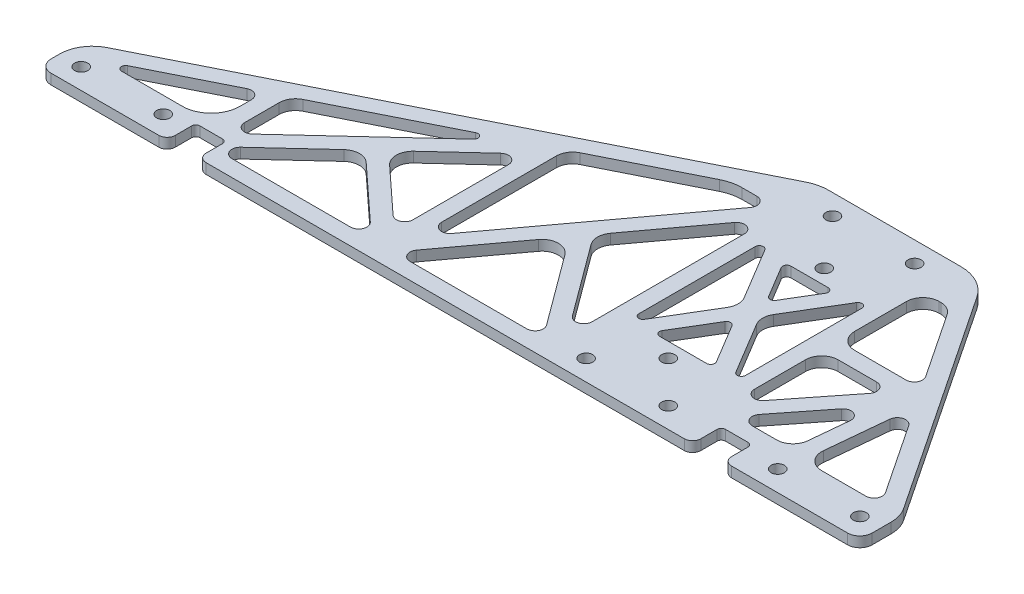
SolidWorks part; units mm, degrees
ref_plane "Front Plane" through (0, 0, 0) normal (0, 0, 1) x (1, 0, 0)
ref_plane "Top Plane" through (0, 0, 0) normal (0, 1, 0) x (1, 0, 0)
ref_plane "Right Plane" through (0, 0, 0) normal (1, 0, 0) x (0, 0, -1)
sketch "Sketch1" plane through (0, 0, 0) normal (0, 1, 0) x (1, 0, 0)
  line L0 (0, 0) -> (254, 0)
  line L2 (203.2, 88.9) -> (152.4, 88.9)
  line L4 (0, 0) -> (0, 12.7)
  line L5 (0, 12.7) -> (152.4, 88.9)
  line L6 (203.2, 88.9) -> (254, 12.7)
  line L7 (254, 12.7) -> (254, 0)
  line L8 (0, 6.35) -> (44.45, 6.35) construction
  line L9 (254, 6.35) -> (222.25, 6.35) construction
  line L10 (139.7, 82.55) -> (207.4333, 82.55) construction
  line L11 (44.45, 0) -> (44.45, 34.925) construction
  line L12 (156.6333, 12.7) -> (154.0933, 7.62)
  line L13 (224.7006, 47.4909) -> (221.314, 12.7) construction
  line L20 (127, 76.2) -> (211.6667, 76.2)
  line L21 (154.0933, 76.2) -> (101.6, 5.08) construction
  line L22 (154.0933, 12.7) -> (154.0933, 7.62)
  line L23 (247.8946, 12.7) -> (194.7333, 12.7)
  line L24 (224.7006, 47.4909) -> (197.2733, 12.7) construction
  line L28 (224.7006, 47.4909) -> (194.7333, 47.4909) construction
  line L31 (5.08, 9.5604) -> (153.5992, 83.82)
  line L32 (200.4813, 83.82) -> (153.5992, 83.82)
  line L33 (200.4813, 83.82) -> (248.92, 11.1619)
  line L34 (248.92, 11.1619) -> (248.92, 5.08)
  line L35 (5.08, 5.08) -> (248.92, 5.08)
  line L36 (5.08, 5.08) -> (5.08, 9.5604)
  line L37 (101.6, 5.08) -> (101.6, 57.8204) construction
  line L39 (127.8467, 40.64) -> (154.0933, 5.08) construction
  line L40 (101.6, 57.8204) -> (44.45, 5.08) construction
  line L41 (73.025, 31.4502) -> (101.6, 5.08) construction
  line L42 (154.0933, 7.62) -> (154.0933, 5.08)
  line L83 (152.8233, 5.08) -> (150.2833, 0)
  line L84 (125.803, 39.1316) -> (152.0497, 3.5716)
  line L107 (152.0497, 77.7084) -> (99.5564, 6.5884)
  line L108 (156.6333, 76.2) -> (194.7333, 12.7) construction
  line L113 (194.7333, 76.2) -> (156.6333, 12.7) construction
  line L117 (104.14, 5.08) -> (104.14, 63.6207)
  line L118 (156.6333, 12.7) -> (194.7333, 12.7)
  line L119 (194.7333, 12.7) -> (201.0833, 0)
  line L120 (154.0933, 6.35) -> (197.9083, 6.35) construction
  line L126 (192.5553, 77.5068) -> (154.4553, 14.0068)
  line L127 (154.4553, 74.8932) -> (192.5553, 11.3932)
  line L128 (156.6333, 12.7) -> (156.6333, 76.2) construction
  line L129 (194.7333, 12.7) -> (194.7333, 76.2) construction
  line L130 (197.2733, 12.7) -> (197.2733, 76.2)
  line L131 (159.1733, 12.7) -> (159.1733, 76.2)
  line L132 (192.1933, 12.7) -> (192.1933, 76.2)
  line L133 (154.0933, 12.7) -> (154.0933, 76.2)
  line L147 (196.9114, 74.8932) -> (158.8114, 11.3932)
  line L148 (158.8114, 77.5068) -> (196.9114, 14.0068)
  line L154 (104.14, 63.6207) -> (42.7274, 6.9466)
  line L155 (71.3024, 29.5836) -> (99.8774, 3.2134)
  line L156 (224.7006, 50.0309) -> (194.7333, 50.0309)
  line L157 (222.7059, 49.0635) -> (195.2786, 14.2725)
  line L158 (197.2733, 12.7) -> (197.2733, 7.62)
  line L159 (222.1726, 47.737) -> (218.7859, 12.9461)
  line L160 (129.8903, 42.1484) -> (156.137, 6.5884)
  line L163 (156.137, 74.6916) -> (103.6436, 3.5716)
  line L164 (99.06, 5.08) -> (99.06, 52.0201)
  line L165 (99.06, 52.0201) -> (46.1726, 3.2134)
  line L166 (175.6833, 19.05) -> (162.9833, 6.35) construction
  line L167 (175.6833, 19.05) -> (188.3833, 6.35) construction
  line L168 (162.9833, 82.55) -> (175.6833, 67.31) construction
  line L169 (175.6833, 67.31) -> (188.3833, 82.55) construction
  line L170 (161.6625, 21.082) -> (189.7041, 21.082) construction
  line L171 (161.6625, 23.622) -> (189.7041, 23.622)
  line L172 (163.1865, 65.278) -> (188.1801, 65.278) construction
  line L173 (163.1865, 62.738) -> (188.1801, 62.738)
  line L174 (74.7476, 33.3168) -> (103.3226, 6.9466)
  line L175 (224.7006, 44.9509) -> (194.7333, 44.9509)
  line L176 (226.6953, 45.9184) -> (199.268, 11.1275)
  line L177 (227.2287, 47.2449) -> (223.842, 12.4539)
  line L178 (8.8192, 11.43) -> (44.45, 11.43)
  line L179 (46.99, 0) -> (46.99, 34.925)
  line L180 (41.91, 0) -> (41.91, 34.925)
  line L181 (198.2745, 13.97) -> (221.4376, 13.97)
  circle A0 centre (6.7733, 6.35) radius 2.032
  circle A1 centre (32.1733, 6.35) radius 2.032
  circle A2 centre (222.25, 6.35) radius 2.032
  circle A3 centre (247.65, 6.35) radius 2.032
  circle A4 centre (162.9833, 82.55) radius 2.032
  circle A5 centre (188.3833, 82.55) radius 2.032
  circle A28 centre (162.9833, 6.35) radius 2.032
  circle A29 centre (188.3833, 6.35) radius 2.032
  arc A32 (197.2733, 12.7) -> (192.1933, 12.7) centre (194.7333, 12.7) cw
  arc A33 (197.2733, 76.2) -> (192.1933, 76.2) centre (194.7333, 76.2) ccw
  arc A34 (159.1733, 12.7) -> (154.0933, 12.7) centre (156.6333, 12.7) cw
  arc A35 (159.1733, 76.2) -> (154.0933, 76.2) centre (156.6333, 76.2) ccw
  arc A45 (192.5553, 77.5068) -> (196.9114, 74.8932) centre (194.7333, 76.2) cw
  arc A46 (154.4553, 14.0068) -> (158.8114, 11.3932) centre (156.6333, 12.7) ccw
  arc A47 (154.4553, 74.8932) -> (158.8114, 77.5068) centre (156.6333, 76.2) cw
  arc A48 (192.5553, 11.3932) -> (196.9114, 14.0068) centre (194.7333, 12.7) ccw
  circle A59 centre (175.6833, 19.05) radius 2.032
  circle A60 centre (175.6833, 67.31) radius 2.032
  arc A61 (125.803, 39.1316) -> (129.8903, 42.1484) centre (127.8467, 40.64) cw
  arc A62 (152.0497, 3.5716) -> (156.137, 6.5884) centre (154.0933, 5.08) ccw
  arc A63 (152.0497, 77.7084) -> (156.137, 74.6916) centre (154.0933, 76.2) cw
  arc A64 (99.5564, 6.5884) -> (103.6436, 3.5716) centre (101.6, 5.08) ccw
  arc A65 (104.14, 5.08) -> (99.06, 5.08) centre (101.6, 5.08) cw
  arc A66 (42.7274, 6.9466) -> (46.1726, 3.2134) centre (44.45, 5.08) ccw
  arc A67 (71.3024, 29.5836) -> (74.7476, 33.3168) centre (73.025, 31.4502) cw
  arc A68 (99.8774, 3.2134) -> (103.3226, 6.9466) centre (101.6, 5.08) ccw
  arc A69 (224.7006, 50.0309) -> (224.7006, 44.9509) centre (224.7006, 47.4909) cw
  arc A70 (194.7333, 50.0309) -> (194.7333, 44.9509) centre (194.7333, 47.4909) ccw
  arc A71 (222.7059, 49.0635) -> (226.6953, 45.9184) centre (224.7006, 47.4909) cw
  arc A72 (195.2786, 14.2725) -> (199.268, 11.1275) centre (197.2733, 12.7) ccw
  arc A73 (222.1726, 47.737) -> (227.2287, 47.2449) centre (224.7006, 47.4909) cw
  arc A74 (218.7859, 12.9461) -> (223.842, 12.4539) centre (221.314, 12.7) ccw
  arc A75 (46.99, 0) -> (41.91, 0) centre (44.45, 0) cw
  arc A76 (46.99, 34.925) -> (41.91, 34.925) centre (44.45, 34.925) ccw
  dimension "D7" = 4.064
  dimension "D8" = 25.4
  dimension "D9" = 130.81
  dimension "D10" = 25.4
  dimension "D11" = 6.35
  dimension "D13" = 19.05
  dimension "D1" = 254
  dimension "D2" = 50.8
  dimension "D3" = 88.9
  dimension "D4" = 152.4
  dimension "D5" = 12.7
  dimension "D6" = 6.35
  dimension "D12" = 25.4
  dimension "D14" = 44.45
  dimension "D15" = 12.7
  dimension "D16" = 57.15
  dimension "D18" = 12.7
  dimension "D19" = 2.54
  dimension "D20" = 50.8
  dimension "D21" = 25.4
  dimension "D22" = 2.54
  dimension "D23" = 6.35
  dimension "D24" = 2.54
  dimension "D29" = 6.35
  dimension "D30" = 38.1
  dimension "D31" = 25.4
  dimension "D32" = 6.35
  dimension "D33" = 2.54
  dimension "D36" = 12.7
  dimension "D38" = 15.24
  dimension "D39" = 2.54
  dimension "D40" = 2.54
  dimension "D27" = 1.27
  dimension "D17" = 5.08
  dimension "D25" = 2.54
  dimension "D26" = 2.54
  dimension "D37" = 2.54
extrude "Boss-Extrude1" add sketch "Sketch1" along normal blind 3.175 contours L0 L7 L6 L2 L5 L4 | A0 | A1 | A5 | A4 | A2 | A3
extrude "Cut-Extrude2" cut sketch "Sketch1<3>" along normal through all contours L154 L31 L11 | L155 L165 L35 | L165 L174 L164 | L117 L107 L20 L31 | L84 L163 L35 | L133 L163 L160 L22 | L157 L175 L130 | L156 L33 L20 L130 | L147 L148 L132 | L131 L126 L127 | L173 L148 L126 | L147 L171 L127 | L33 L177 L23 | L178 L180 L31 | L176 L181 L159 | A28 | A59 | A29 | A60 region at (30.8797, 0, -16.9451) region at (73.025, 0, -12.718) region at (62.4687, 0, -31.7097) region at (120.7695, 0, -51.2726) region at (127.8467, 0, -15.5076) region at (91.6301, 0, -31.4502) region at (206.5243, 0, -60.8789) region at (146.3968, 0, -40.64) region at (204.6702, 0, -35.5682) region at (175.6833, 0, -28.919) region at (187.6774, 0, -44.45) region at (213.9093, 0, -22.3524) region at (163.6893, 0, -44.45) region at (232.896, 0, -23.1836) region at (175.6833, 0, -58.2876)
sketch "Sketch1<3>" plane through (0, 0, 0) normal (0, 1, 0) x (1, 0, 0) same geometry as "Sketch1"
fillet "Fillet1" radius 3.81 2 edges at (254, 1.5875, 0) (0, 1.5875, 0)
fillet "Fillet2" radius 10.16 2 edges at (254, 1.5875, -12.7) (0, 1.5875, -12.7)
fillet "Fillet3" radius 12.7 2 edges at (203.2, 1.5875, -88.9) (152.4, 1.5875, -88.9)
fillet "Fillet4" radius 1.27 12 edges at (159.1733, 1.5875, -67.0298) (192.1933, 1.5875, -67.0298) (192.1933, 1.5875, -21.8702) (159.1733, 1.5875, -21.8702) (183.694, 1.5875, -62.738) (167.6727, 1.5875, -62.738) (175.6833, 1.5875, -49.3869) (185.218, 1.5875, -23.622) (166.1487, 1.5875, -23.622) (175.6833, 1.5875, -39.5131) (93.426, 1.5875, -53.7334) (8.8192, 1.5875, -11.43)
fillet "Fillet5" radius 2.54 19 edges at (223.0073, 1.5875, -50.0309) (247.8946, 1.5875, -12.7) (226.9275, 1.5875, -44.1507) (221.3335, 1.5875, -39.1171) (197.2733, 1.5875, -16.8027) (219.4639, 1.5875, -44.9509) (104.14, 1.5875, -12.7984) (99.06, 1.5875, -52.0201) (48.1953, 1.5875, -5.08) (97.8547, 1.5875, -5.08) (99.06, 1.5875, -10.8803) (104.7569, 1.5875, -5.08) (150.9364, 1.5875, -5.08) (154.0933, 1.5875, -9.3572) (154.0933, 1.5875, -71.9228) (150.9364, 1.5875, -76.2) (41.91, 1.5875, -27.9754) (46.99, 1.5875, -10.8803) (201.5089, 1.5875, -13.97)
fillet "Fillet6" radius 5.08 14 edges at (172.7212, 1.5875, -44.45) (178.6455, 1.5875, -44.45) (223.866, 1.5875, -12.7) (197.2733, 1.5875, -50.0309) (197.2733, 1.5875, -44.9509) (197.2733, 1.5875, -76.2) (205.5613, 1.5875, -76.2) (73.025, 1.5875, -27.9939) (76.7703, 1.5875, -31.4502) (104.14, 1.5875, -59.0904) (131.0036, 1.5875, -40.64) (127.8467, 1.5875, -36.3628) (46.99, 1.5875, -30.5154) (218.8856, 1.5875, -13.97)
fillet "Fillet7" radius 12.7 1 edges at (138.3592, 1.5875, -76.2)
fillet "Fillet10" radius 8.89 1 edges at (41.91, 1.5875, -11.43)
sketch "Sketch2" plane through (0, 3.175, 0) normal (0, 1, 0) x (1, 0, 0)
  line L0 (39.6875, 0) -> (39.6875, 8.89)
  line L1 (3.81, 0) -> (250.19, 0) construction
  line L2 (39.6875, 8.89) -> (49.2125, 8.89)
  line L3 (49.2125, 8.89) -> (49.2125, 0)
  line L4 (0, 3.81) -> (0, 6.4208) construction
  line L5 (202.2475, 0) -> (202.2475, 8.89)
  line L6 (202.2475, 8.89) -> (211.7725, 8.89)
  line L7 (211.7725, 8.89) -> (211.7725, 0)
  line L8 (254, 9.6238) -> (254, 3.81) construction
  line L9 (3.81, 0) -> (250.19, 0)
  dimension "D1" = 39.6875
  dimension "D2" = 9.525
  dimension "D3" = 8.89
  dimension "D4" = 42.2275
extrude "Cut-Extrude3" cut sketch "Sketch2" against normal through all contours L0 L9 L3 L2 | L5 L9 L7 L6 region at (207.01, 3.175, -4.445) region at (44.45, 3.175, -4.445)
fillet "Fillet8" radius 1.27 4 edges at (211.7725, 1.5875, -8.89) (202.2475, 1.5875, -8.89) (49.2125, 1.5875, -8.89) (39.6875, 1.5875, -8.89)
fillet "Fillet9" radius 2.54 4 edges at (49.2125, 1.5875, 0) (39.6875, 1.5875, 0) (211.7725, 1.5875, 0) (202.2475, 1.5875, 0)
